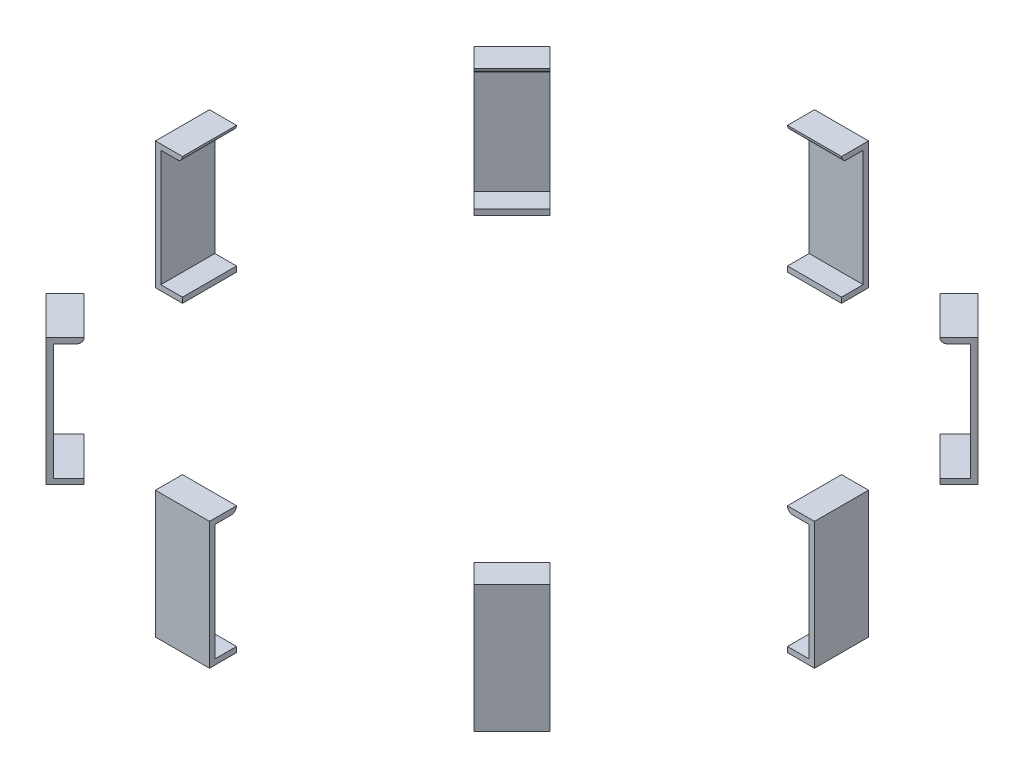
SolidWorks part; units mm, degrees
ref_plane "Front Plane" through (0, 0, 0) normal (0, 0, 1) x (1, 0, 0)
ref_plane "Top Plane" through (0, 0, 0) normal (0, 1, 0) x (1, 0, 0)
ref_plane "Right Plane" through (0, 0, 0) normal (1, 0, 0) x (0, 0, -1)
sketch "Sketch1" plane through (0, 0, 0) normal (0, 1, 0) x (1, 0, 0)
  line L0 (0, -55) -> (0, 55) construction
  line L1 (5, 61) -> (-5, 61)
  line L2 (5, 61) -> (5, 56)
  line L3 (5, 56) -> (-5, 56)
  line L4 (-5, 61) -> (-5, 56)
  circle A0 centre (0, 0) radius 60.5 construction
  point P3 (0, 60.5)
  point P14 (0, 61)
  dimension "D1" = 121
  dimension "D2" = 5
  dimension "D3" = 61
  dimension "D4" = 10
extrude "Boss-Extrude1" add sketch "Sketch1" along normal blind 1
sketch "Sketch2" plane through (0, 1, 0) normal (0, 1, 0) x (1, 0, 0)
  line L0 (5, 56) -> (5, 61) construction
  line L1 (-5, 61) -> (5, 61)
  line L2 (-5, 61) -> (-5, 60)
  line L3 (-5, 60) -> (5, 60)
  line L4 (5, 61) -> (5, 60)
  line L5 (-5, 61) -> (5, 60) construction
  line L6 (-5, 60) -> (5, 61) construction
  point P4 (0, 60.5)
  dimension "D1" = 1
extrude "Boss-Extrude2" add sketch "Sketch2" along normal blind 22.55
sketch "Sketch3" plane through (0, 0, -60) normal (0, 0, 1) x (1, 0, 0)
  line L0 (-5, 23.55) -> (-5, 1) construction
  line L1 (-5, 22.55) -> (5, 22.55)
  line L2 (-5, 22.55) -> (-5, 23.55)
  line L3 (-5, 23.55) -> (5, 23.55)
  line L4 (5, 22.55) -> (5, 23.55)
  line L5 (-5, 22.55) -> (5, 23.55) construction
  line L6 (-5, 23.55) -> (5, 22.55) construction
  point P4 (0, 23.05)
  dimension "D1" = 1
extrude "Boss-Extrude3" add sketch "Sketch3" along normal up to surface (4 mm away) up to face at (0, 0.5, -56)
fillet "Fillet1" radius 1 1 edges at (0, 22.55, -56)
ref_axis "Axis1" through (0, 23.625, 0) along (0, -1, 0)
pattern_circular "CirPattern1" count 8 over 360 about axis through (0, 23.625, 0) along (0, -1, 0) of bodies 103
